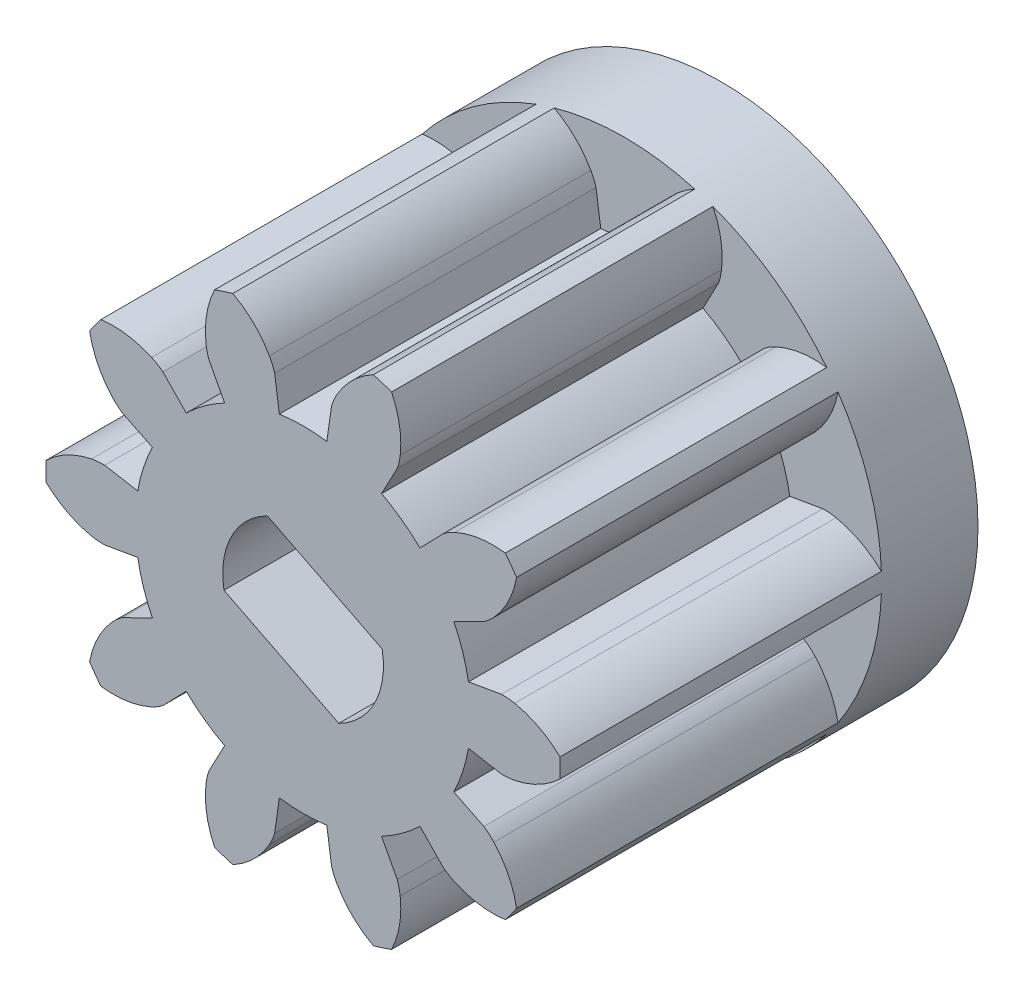
SolidWorks part; units mm, degrees
ref_plane "Plano frontal" through (0, 0, 0) normal (0, 0, 1) x (1, 0, 0)
ref_plane "Plano superior" through (0, 0, 0) normal (0, 1, 0) x (1, 0, 0)
ref_plane "Plano direito" through (0, 0, 0) normal (1, 0, 0) x (0, 0, -1)
sketch "Esboço1" plane through (0, 0, -24.3983) normal (0, 0, 1) x (1, 0, 0)
  line L0 (156.8059, -4.5413) -> (153.2345, -2.7399)
  line L1 (155.4549, -7.2198) -> (151.8834, -5.4184)
  arc A0 (156.8059, -4.5413) -> (155.4549, -7.2198) centre (154.3447, -4.9798) cw
  arc A2 (151.8834, -5.4184) -> (153.2345, -2.7399) centre (154.3447, -4.9798) cw
  circle A3 centre (154.3447, -4.9798) radius 8
  dimension "D1" = 16
extrude "Ressalto-extrusão1" add sketch "Esboço1" along normal up to surface (13 mm away)
sketch "Esboço4" plane through (0, 0, -11.3983) normal (0, 0, 1) x (1, 0, 0)
  line L0 (155.083, -10.1499) -> (155.2303, -11.1819)
  line L1 (154.3447, -4.9798) -> (154.3447, -12.9798) construction
  line L2 (153.6064, -10.1499) -> (153.459, -11.1819)
  circle A0 centre (154.3447, -4.9798) radius 5.2225 construction
  circle A1 centre (154.3447, -4.9798) radius 6.265 construction
  circle A2 centre (154.3447, -4.9798) radius 6.665 construction
  arc A4 (155.2303, -11.1819) -> (155.3917, -11.5621) centre (156.975, -10.6659) ccw
  arc A5 (155.3917, -11.5621) -> (156.532, -12.675) centre (157.8831, -10.1499) ccw
  arc A6 (153.459, -11.1819) -> (153.2977, -11.5621) centre (151.7143, -10.6659) cw
  arc A7 (153.2977, -11.5621) -> (152.1573, -12.675) centre (150.8062, -10.1499) cw
  arc A8 (155.083, -10.1499) -> (153.6064, -10.1499) centre (154.3447, -4.9798) cw
  arc A9 (156.532, -12.675) -> (152.1573, -12.675) centre (154.3447, -4.9798) cw
  circle A10 centre (154.3447, -4.9798) radius 8 construction
  point P17 (155.1567, -10.6659)
  dimension "D1" = 13.33
  dimension "D2" = 10.445
  dimension "D3" = 12.53
  dimension "D4" = 2.094
extrude "Corte-extrusão1" cut sketch "Esboço4" against normal blind 10
pattern_circular "PadrãoCircular1" count 10 over 360 about axis through (154.3447, -4.9798, -11.3983) along (0, 0, -1) of "Corte-extrusão1"
